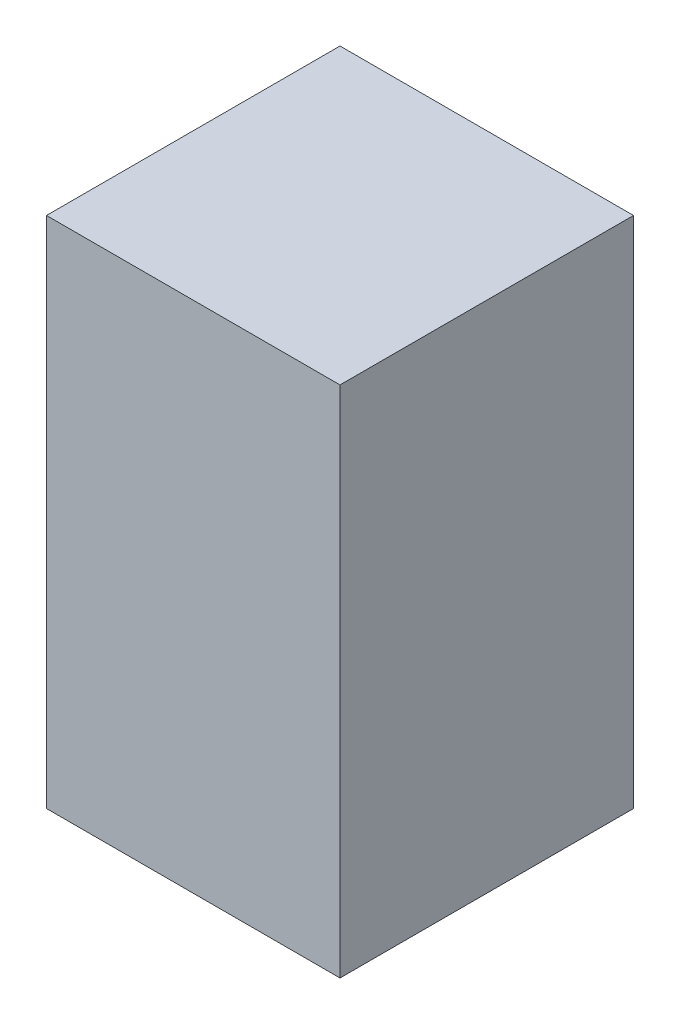
SolidWorks part; units mm, degrees
ref_plane "Front" through (0, 0, 0) normal (0, 0, 1) x (1, 0, 0)
ref_plane "Top" through (0, 0, 0) normal (0, 1, 0) x (1, 0, 0)
ref_plane "Right" through (0, 0, 0) normal (1, 0, 0) x (0, 0, -1)
sketch "Sketch1" plane through (0, 0, 0) normal (0, 1, 0) x (1, 0, 0)
  line L1 (-609.6, -609.6) -> (609.6, -609.6)
  line L2 (-609.6, -609.6) -> (-609.6, 609.6)
  line L3 (-609.6, 609.6) -> (609.6, 609.6)
  line L4 (609.6, -609.6) -> (609.6, 609.6)
  line L5 (-609.6, -609.6) -> (609.6, 609.6) construction
  line L6 (-609.6, 609.6) -> (609.6, -609.6) construction
  point P0 (0, 0)
  dimension "D1" = 1219.2
extrude " Illuminance Plane 2-27-2019 10:35:29 AM" add sketch "Sketch1" along normal blind 2133.6
